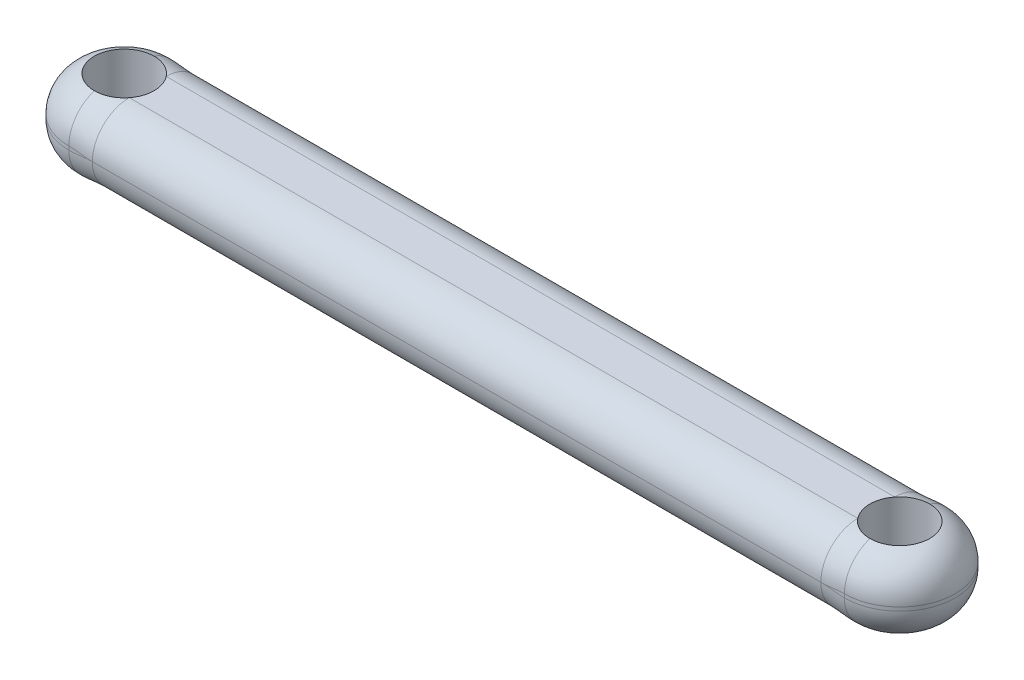
SolidWorks part; units mm, degrees
ref_plane "Alzado" through (0, 0, 0) normal (1, 0, 0) x (0, 1, 0)
ref_plane "Planta" through (0, 0, 0) normal (0, 0, 1) x (0, 1, 0)
ref_plane "Vista lateral" through (0, 0, 0) normal (0, 1, 0) x (-1, 0, 0)
sketch "Croquis1" plane through (0, 0, 0) normal (0, 1, 0) x (-1, 0, 0)
  line L0 (0, 0) -> (105, 0) construction
  line L1 (0, 0) -> (105, 0) construction
  line L2 (0, 7.5) -> (105, 7.5)
  line L3 (0, -7.5) -> (105, -7.5)
  arc A0 (0, 7.5) -> (0, -7.5) centre (0, 0) ccw
  arc A1 (105, -7.5) -> (105, 7.5) centre (105, 0) ccw
  circle A2 centre (0, 0) radius 4.05
  circle A3 centre (105, 0) radius 4.05
  point P3 (52.5, 0)
  dimension "D3" = 8.1
  dimension "D1" = 105
  dimension "D2" = 15
extrude "Saliente-Extruir1" add sketch "Croquis1" along normal mid plane 10
fillet "Redondeo1" radius 5 8 edges at (7.5, 5, 0) (-52.5, 5, 7.5) (-112.5, 5, 0) (7.5, -5, 0) (-52.5, -5, 7.5) (-112.5, -5, 0) (-52.5, 5, -7.5) (-52.5, -5, -7.5)
equation "\"ancho\"= 15"
equation "\"esp\"= 10"
equation "\"Lbarra05\"=105"
equation "\"agujeros\"=8.1"
equation "\"D1@Croquis1\"=\"Lbarra05\""
equation "\"D2@Croquis1\"=\"ancho\""
equation "\"D3@Croquis1\"=\"agujeros\""
equation "\"D1@Saliente-Extruir1\"=\"esp\""
equation "\"D1@Redondeo1\"=\"esp\"/2"
